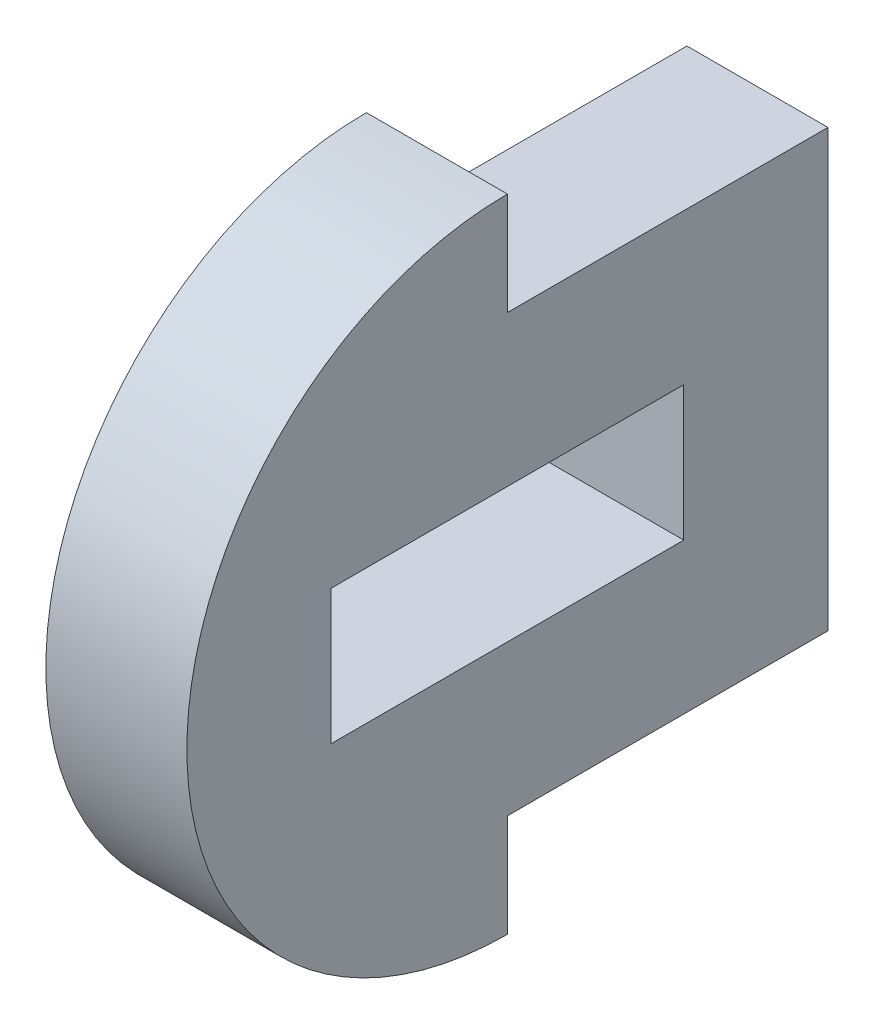
SolidWorks part; units mm, degrees
ref_plane "Front Plane" through (0, 0, 0) normal (0, 0, 1) x (1, 0, 0)
ref_plane "Top Plane" through (0, 0, 0) normal (0, 1, 0) x (1, 0, 0)
ref_plane "Right Plane" through (0, 0, 0) normal (1, 0, 0) x (0, 0, -1)
sketch "Sketch1" plane through (0, 0, 0) normal (1, 0, 0) x (0, 0, -1)
  line L0 (0, 10) -> (0, 6.8)
  line L1 (0, 6.8) -> (10, 6.8)
  line L2 (10, 6.8) -> (10, -6.8)
  line L3 (10, -6.8) -> (0, -6.8)
  line L4 (0, -6.8) -> (0, -10)
  line L6 (-5.5, 2.1) -> (5.5, 2.1)
  line L7 (-5.5, 2.1) -> (-5.5, -2.1)
  line L8 (-5.5, -2.1) -> (5.5, -2.1)
  line L9 (5.5, 2.1) -> (5.5, -2.1)
  arc A0 (0, 10) -> (0, -10) centre (0, 0) ccw
  dimension "D1" = 20
  dimension "D2" = 3.2
  dimension "D3" = 3.2
  dimension "D4" = 10
  dimension "D5" = 11
  dimension "D6" = 5.5
  dimension "D7" = 4.2
  dimension "D8" = 2.1
extrude "Boss-Extrude1" add sketch "Sketch1" along normal blind 4.4
equation "\"fit\" = 1"
equation "\"phone thick\"= 9.5"
equation "\"phone support width\" = 10"
equation "\"Thicker acrylic\"= 4.4"
equation "\"Thinner acrylic\"= 3.2"
equation "\"D4@Sketch1\"=10"
equation "\"D5@Sketch1\"=\"phone support width\"+\"fit\""
equation "\"D6@Sketch1\"=\"D5@Sketch1\"/2"
equation "\"D7@Sketch1\"=\"Thinner acrylic\"+\"fit\""
equation "\"D8@Sketch1\"=\"D7@Sketch1\"/2"
equation "\"Phone segment thick\"= 20"
equation "\"D1@Sketch1\"=\"Phone segment thick\""
equation "\"D2@Sketch1\"=\"Thinner acrylic\""
equation "\"D3@Sketch1\"=\"Thinner acrylic\""
